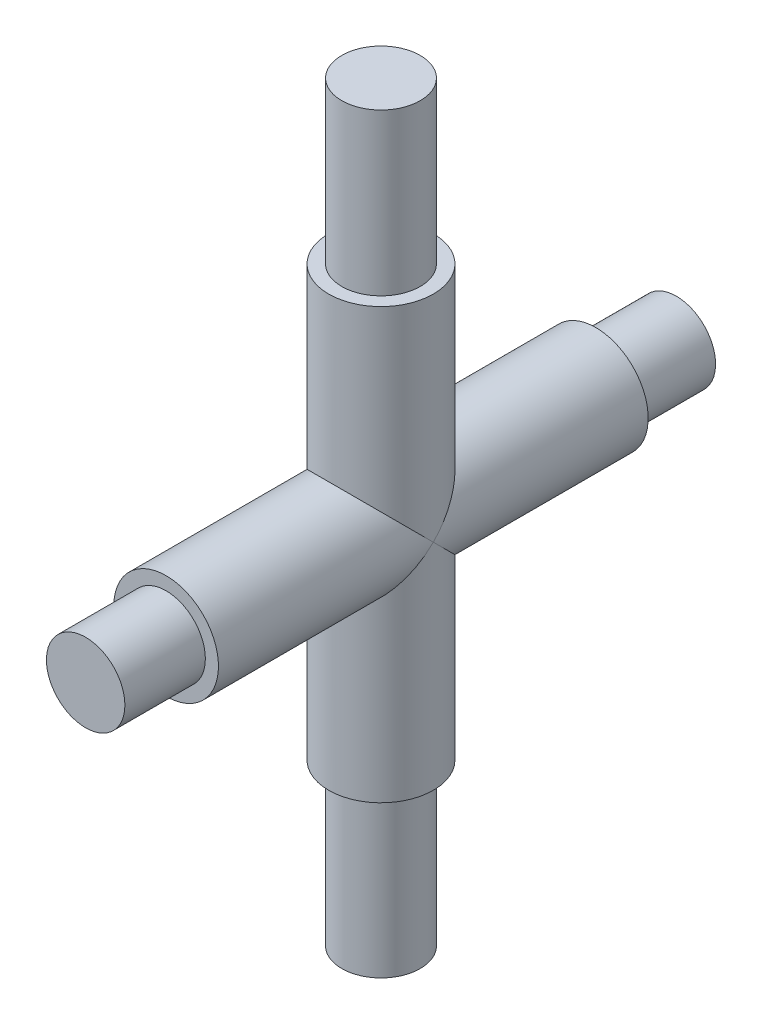
SolidWorks part; units mm, degrees
ref_plane "Front Plane" through (0, 0, 0) normal (0, 0, 1) x (1, 0, 0)
ref_plane "Top Plane" through (0, 0, 0) normal (0, 1, 0) x (1, 0, 0)
ref_plane "Right Plane" through (0, 0, 0) normal (1, 0, 0) x (0, 0, -1)
sketch "Sketch1" plane through (0, 0, 0) normal (0, 1, 0) x (1, 0, 0)
  circle A1 centre (0, 0) radius 6.5
  dimension "D1" = 13
extrude "Boss-Extrude1" add sketch "Sketch1" along normal blind 53.4
sketch "Sketch11" plane through (0, 0, 0) normal (0, -1, 0) x (-1, 0, 0)
  circle A0 centre (0, 0) radius 4.875
  dimension "D1" = 9.75
extrude "Boss-Extrude2" add sketch "Sketch11" along normal blind 20
sketch "Sketch12" plane through (0, 53.4, 0) normal (0, 1, 0) x (1, 0, 0)
  circle A0 centre (0, 0) radius 4.875
  dimension "D1" = 9.75
extrude "Boss-Extrude3" add sketch "Sketch12" along normal blind 20
sketch3d "3DSketch1"
  line L0 (0, -20, 0) -> (0, 73.4, 0) construction
  line L1 (0, -20, 0) -> (0, 0, 0) construction
  line L2 (0, 73.4, 0) -> (0, 53.4, 0) construction
  line L3 (0, 26.7, 0) -> (29.5521, 26.7, 0) construction
pattern_circular "CirPattern1" count 2 over 360 about axis through (0, 26.7, 0) along (1, 0, 0) of "Boss-Extrude1", "Boss-Extrude2", "Boss-Extrude3"
ref_plane "Plane1" through (0, 0, 0) normal (0, 0, -1) x (-1, 0, 0)
sketch "Sketch13" plane through (0, 0, 0) normal (0, 0, -1) x (-1, 0, 0)
  circle A0 centre (0, 26.7) radius 6.5
extrude "Boss-Extrude4" add sketch "Sketch13" along normal blind 26.7 and the other way blind 26.7
sketch "Sketch14" plane through (0, 0, -26.7) normal (0, 0, -1) x (-1, 0, 0)
  circle A0 centre (0, 26.7) radius 4.875
  dimension "D1" = 9.75
extrude "Boss-Extrude5" add sketch "Sketch14" along normal blind 10
sketch "Sketch15" plane through (0, 0, 26.7) normal (0, 0, 1) x (1, 0, 0)
  circle A0 centre (0, 26.7) radius 4.875
  dimension "D1" = 9.75
extrude "Boss-Extrude6" add sketch "Sketch15" along normal blind 10
